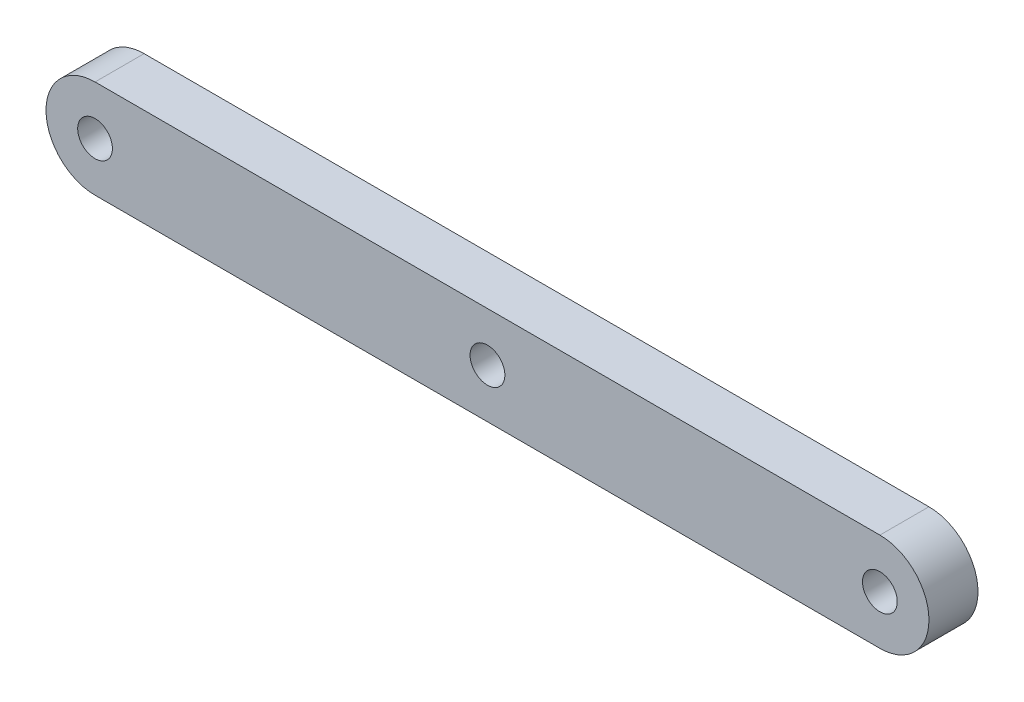
SolidWorks part; units mm, degrees
ref_plane "Front Plane" through (0, 0, 0) normal (0, 0, 1) x (1, 0, 0)
ref_plane "Top Plane" through (0, 0, 0) normal (0, 1, 0) x (1, 0, 0)
ref_plane "Right Plane" through (0, 0, 0) normal (1, 0, 0) x (0, 0, -1)
sketch "Sketch1" plane through (0, 0, 0) normal (0, 0, 1) x (1, 0, 0)
  line L0 (0, 0) -> (101.6, 0) construction
  line L1 (0, 6.35) -> (101.6, 6.35)
  line L2 (0, -6.35) -> (101.6, -6.35)
  arc A0 (0, 6.35) -> (0, -6.35) centre (0, 0) ccw
  arc A1 (101.6, -6.35) -> (101.6, 6.35) centre (101.6, 0) ccw
  circle A2 centre (101.6, 0) radius 2.575 construction
  circle A3 centre (50.8, 0) radius 2.0625 construction
  point P3 (50.8, 0)
  dimension "D2" = 6.35
  dimension "D3" = 5.15
  dimension "D4" = 4.125
  dimension "D1" = 101.6
extrude "Boss-Extrude1" add sketch "Sketch1" along normal blind 6.35
sketch "Sketch2" plane through (0, 0, 6.35) normal (0, 0, 1) x (1, 0, 0)
  line L0 (0, 0) -> (101.6, 0) construction
  line L1 (-1.3843, 0.4953) -> (1.3843, 0.4953)
  line L2 (-1.3843, 0.4953) -> (-1.3843, -0.4953)
  line L3 (-1.3843, -0.4953) -> (1.3843, -0.4953)
  line L4 (1.3843, 0.4953) -> (1.3843, -0.4953)
  line L5 (0, -0.4953) -> (0, 0.4953) construction
  line L6 (-1.3843, 0) -> (1.3843, 0) construction
  point P88 (0, 0)
  dimension "D1" = 0.9906
  dimension "D2" = 2.7686
extrude "Cut-Extrude1" [suppressed] cut sketch "Sketch2" against normal blind 6.35
hole_wizard "M4 Clearance Hole2" positions "Sketch3" profile "Sketch4" hole size "M4" standard "ANSI Metric" end condition through all
sketch "Sketch3" plane through (0, 0, 0) normal (0, 0, -1) x (-1, 0, 0)
  point P0 (-101.6, 0)
sketch "Sketch4" plane through (101.6, 0, 0) normal (1, 0, 0) x (0, 1, 0)
  line L0 (0, 0) -> (0, 6.35)
  line L1 (0, 6.35) -> (2.25, 6.35)
  line L2 (2.25, 6.35) -> (2.25, 0)
  line L5 (2.25, 0) -> (0, 0)
  line L11 (0, -6.35) -> (0, 107.95) construction
  dimension "Thru Hole Dia." = 4.5
  dimension "Thru Hole Depth" = 6.35
hole_wizard "M4 Clearance Hole1" positions "Sketch5" profile "Sketch6" hole size "M4" standard "ANSI Metric" end condition through all
sketch "Sketch5" plane through (0, 0, 0) normal (0, 0, -1) x (-1, 0, 0)
  point P0 (-50.8, 0)
sketch "Sketch6" plane through (50.8, 0, 0) normal (1, 0, 0) x (0, 1, 0)
  line L0 (0, 0) -> (0, 6.35)
  line L1 (0, 6.35) -> (2.25, 6.35)
  line L2 (2.25, 6.35) -> (2.25, 0)
  line L5 (2.25, 0) -> (0, 0)
  line L11 (0, -6.35) -> (0, 107.95) construction
  dimension "Thru Hole Dia." = 4.5
  dimension "Thru Hole Depth" = 6.35
ref_axis "Axis1" through (50.8, 0, 6.35) along (0, 0, -1)
ref_plane "Plane1" through (50.8, 0, 0) normal (1, 0, 0) x (0, 0, -1)
mirror "Mirror1" about plane through (50.8, 0, 0) normal (1, 0, 0) of "M4 Clearance Hole2"
equation "\"spring width\"= .099in"
equation "\"spring thick\"= .029in"
equation "\"stock thick\"= .25in"
equation "\"D1@Boss-Extrude1\"=\"stock thick\""
equation "\"D1@Sketch2\"=\"spring thick\" + .01"
equation "\"D2@Sketch2\"=\"spring width\" + .01"
equation "\"D1@Cut-Extrude1\"=\"stock thick\""
